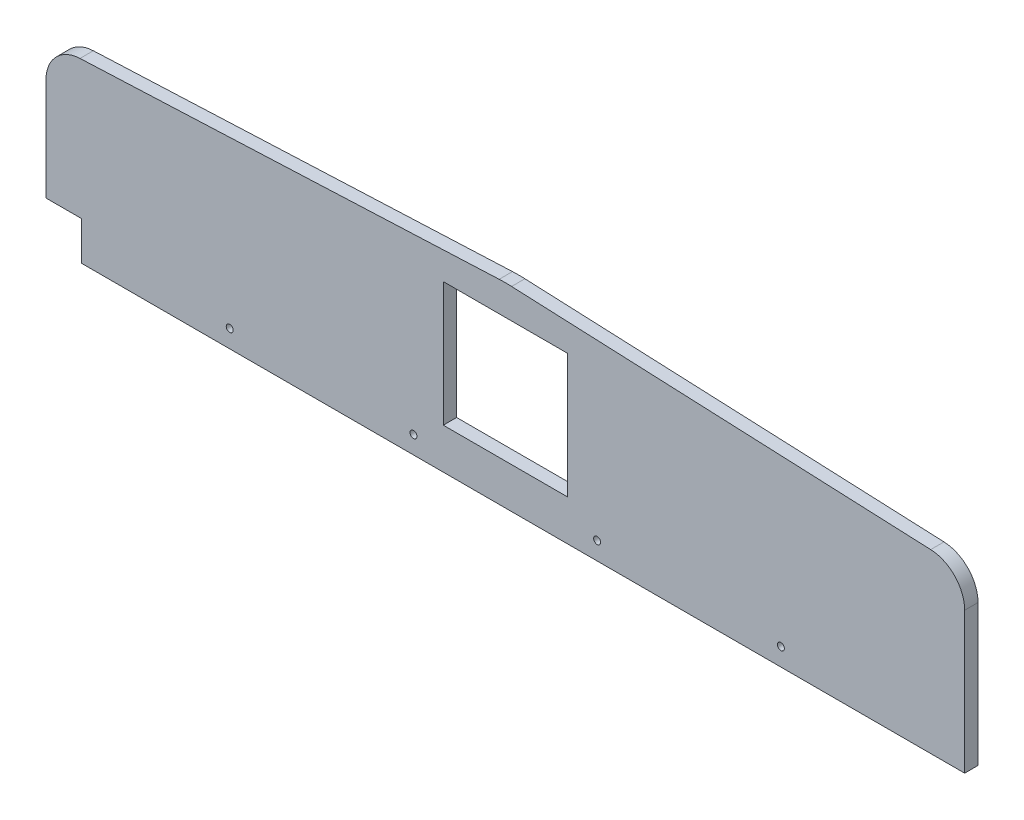
SolidWorks part; units mm, degrees
material "PC High Viscosity"
ref_plane "Front Plane" through (0, 0, 0) normal (0, 0, 1) x (1, 0, 0)
ref_plane "Top Plane" through (0, 0, 0) normal (0, 1, 0) x (1, 0, 0)
ref_plane "Right Plane" through (0, 0, 0) normal (1, 0, 0) x (0, 0, -1)
sketch "Sketch2" plane through (0, 0, 0) normal (0, 0, 1) x (1, 0, 0)
  line L0 (-328.3315, 55.6895) -> (-328.3315, 154.4895)
  line L1 (-328.3315, 154.4895) -> (0, 168.8465)
  line L2 (0, 168.8465) -> (328.2858, 154.4895)
  line L3 (328.2858, 154.4895) -> (328.2858, 55.6895)
  line L4 (328.2858, 55.6895) -> (328.2858, 29.2895)
  line L6 (328.2858, 29.2895) -> (-328.3315, 29.2895)
  line L7 (-328.3315, 29.2895) -> (-328.3315, 55.6895)
  dimension "D1" = 113.157
  dimension "D7" = 328.2858
  dimension "D8" = 98.8
  dimension "D9" = 26.4
extrude "Boss-Extrude1" add sketch "Sketch2" along normal mid plane 9.525
fillet "Fillet1" radius 25.4 2 edges at (328.2858, 154.4895, 0) (-328.3315, 154.4895, 0)
fillet "Fillet2" radius 101.6 1 edges at (0, 168.8465, 0)
sketch "Sketch3" plane through (0, 0, 4.7625) normal (0, 0, 1) x (1, 0, 0)
  line L0 (0, 0) -> (0, 192.0016) construction
  line L1 (-328.3315, 29.2895) -> (-302.9315, 29.2895)
  line L2 (-328.3315, 29.2895) -> (-328.3315, 56.9755)
  line L3 (-328.3315, 56.9755) -> (-302.9315, 56.9755)
  line L4 (-302.9315, 29.2895) -> (-302.9315, 56.9755)
  line L5 (0, 192.0016) -> (0, -60.0751) construction
  dimension "D1" = 25.4
  dimension "D2" = 27.686
extrude "Cut-Extrude1" cut sketch "Sketch3" against normal through all
sketch "Sketch5" plane through (0, 0, 4.7625) normal (0, 0, 1) x (1, 0, 0)
  line L1 (-44.3827, 147.2687) -> (44.5173, 147.2687)
  line L2 (-44.3827, 147.2687) -> (-44.3827, 58.3687)
  line L3 (-44.3827, 58.3687) -> (44.5173, 58.3687)
  line L4 (44.5173, 147.2687) -> (44.5173, 58.3687)
  line L5 (-44.3827, 147.2687) -> (44.5173, 58.3687) construction
  line L6 (-44.3827, 58.3687) -> (44.5173, 147.2687) construction
  point P0 (0.0673, 102.8187)
  dimension "D1" = 88.9
  dimension "D2" = 88.9
extrude "Cut-Extrude2" cut sketch "Sketch5" against normal through all
hole_wizard "Tap Drill for M6x1.0 Tap1" positions "Sketch7" profile "Sketch6" hole size "M6x1.0" standard "ANSI Metric" end condition through all
sketch "Sketch7" plane through (0, 0, 4.7625) normal (0, 0, 1) x (1, 0, 0)
  line L0 (-302.9315, 29.2895) -> (328.2858, 29.2895) construction
  line L1 (-328.3315, 130.1759) -> (-328.3315, 56.9755) construction
  point P0 (-197.0135, 41.9895)
  point P2 (-65.6955, 41.9895)
  point P4 (65.6225, 41.9895)
  point P6 (196.9405, 41.9895)
  dimension "D1" = 12.7
  dimension "D2" = 131.318
  dimension "D3" = 131.318
  dimension "D4" = 131.318
  dimension "D5" = 131.318
sketch "Sketch6" plane through (-197.0135, 41.9895, 4.7625) normal (1, 0, 0) x (0, -1, 0)
  line L0 (0, 0) -> (0, 9.525)
  line L1 (0, 9.525) -> (2.5, 9.525)
  line L2 (2.5, 9.525) -> (2.5, 0)
  line L5 (2.5, 0) -> (0, 0)
  line L11 (0, -6.35) -> (0, 107.95) construction
  dimension "Thru Hole Dia." = 5
  dimension "Thru Hole Depth" = 9.525
